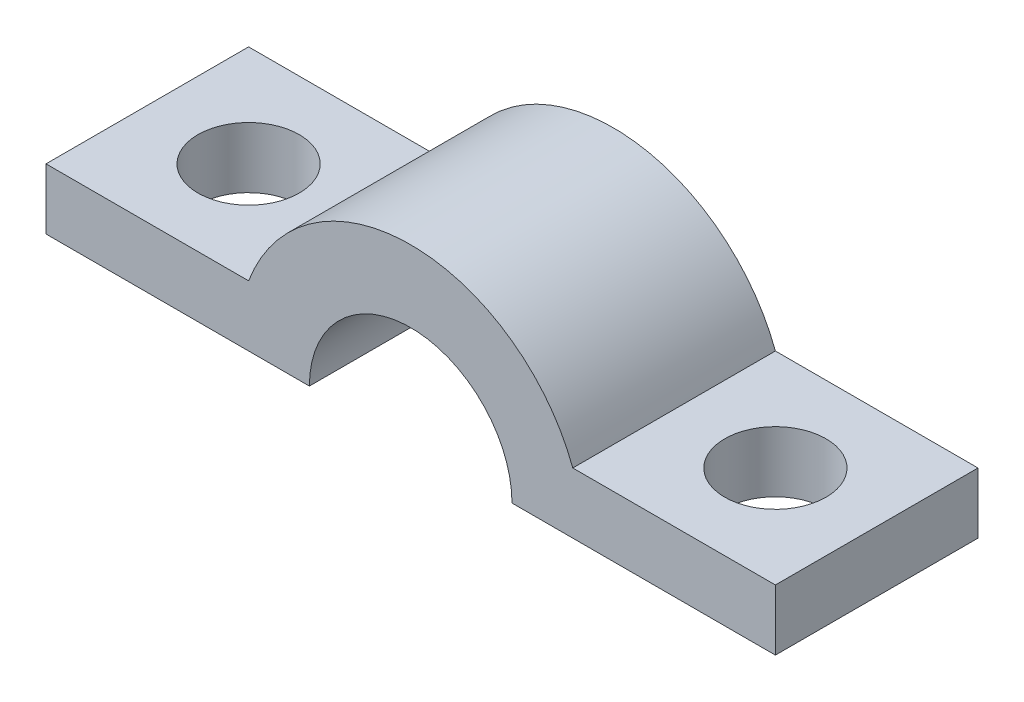
SolidWorks part; units mm, degrees
ref_plane "Front Plane" through (0, 0, 0) normal (0, 0, 1) x (1, 0, 0)
ref_plane "Top Plane" through (0, 0, 0) normal (0, 1, 0) x (1, 0, 0)
ref_plane "Right Plane" through (0, 0, 0) normal (1, 0, 0) x (0, 0, -1)
sketch "Sketch1" plane through (0, 0, 0) normal (0, 0, 1) x (1, 0, 0)
  line L0 (-3.81, 3.81) -> (-16.51, 3.81)
  line L1 (-16.51, 3.81) -> (-16.51, 0)
  line L2 (-16.51, 0) -> (0, 0)
  line L3 (6.35, 0) -> (6.35, 10.8509) construction
  line L4 (29.21, 0) -> (12.7, 0)
  line L5 (29.21, 3.81) -> (29.21, 0)
  line L6 (16.51, 3.81) -> (29.21, 3.81)
  arc A0 (0, 0) -> (12.7, 0) centre (6.35, 0) cw
  arc A1 (-3.81, 3.81) -> (16.51, 3.81) centre (6.35, 0) cw
  point P9 (6.35, 10.8509)
  dimension "D1" = 12.7
  dimension "D2" = 3.81
  dimension "D3" = 3.81
  dimension "D4" = 12.7
extrude "Boss-Extrude1" add sketch "Sketch1" along normal blind 12.7
sketch "Sketch2" plane through (0, 3.81, 0) normal (0, 1, 0) x (1, 0, 0)
  line L0 (-10.16, 0) -> (-10.16, -12.7) construction
  line L1 (-3.81, 0) -> (-16.51, 0) construction
  line L2 (-3.81, -12.7) -> (-16.51, -12.7) construction
  line L3 (-16.51, -6.35) -> (-3.81, -6.35) construction
  line L4 (-16.51, -12.7) -> (-16.51, 0) construction
  line L5 (-3.81, -12.7) -> (-3.81, 0) construction
  line L6 (6.35, 0) -> (6.35, -12.7) construction
  line L7 (16.51, 0) -> (-3.81, 0) construction
  line L8 (-3.81, -12.7) -> (16.51, -12.7) construction
  circle A0 centre (-10.16, -6.35) radius 3.175
  circle A1 centre (22.86, -6.35) radius 3.175
  point P15 (-10.16, -6.35)
  dimension "D1" = 6.35
extrude "Cut-Extrude1" cut sketch "Sketch2" against normal through all
